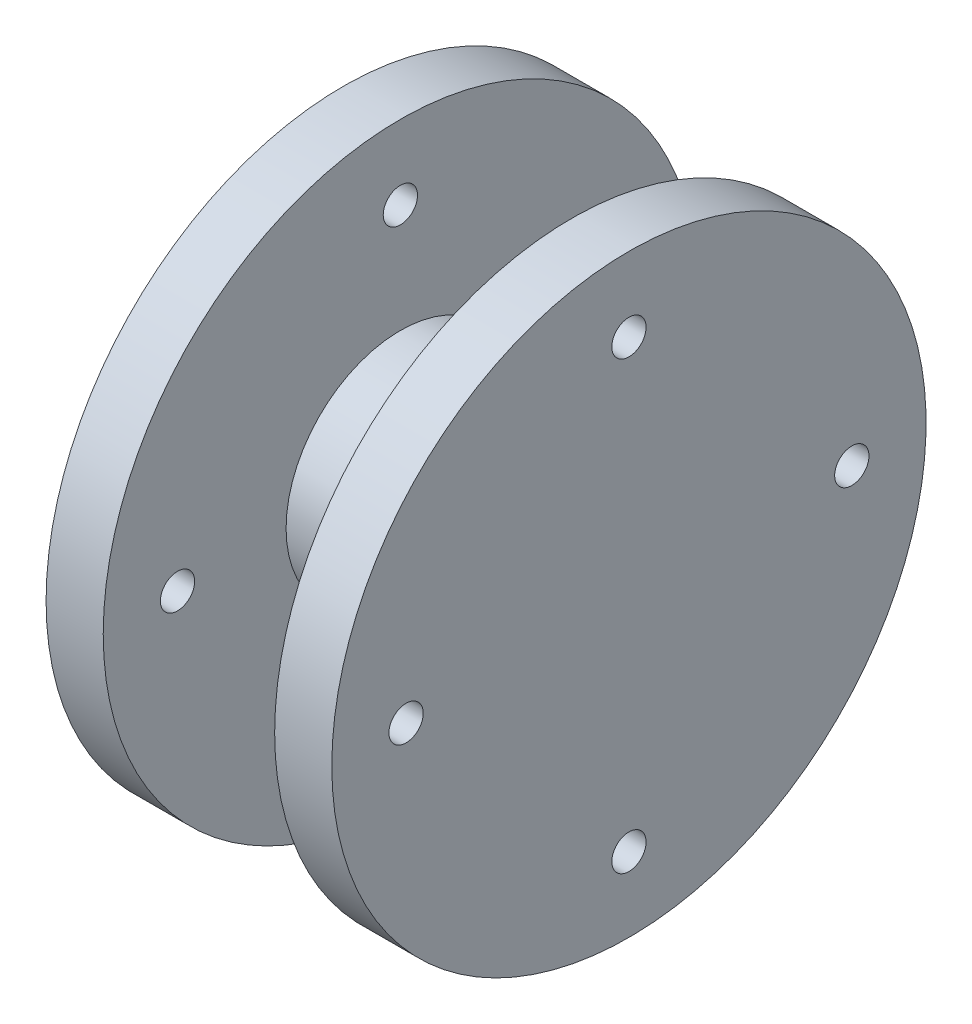
SolidWorks part; units mm, degrees
ref_plane "Спереди" through (0, 0, 0) normal (0, 0, 1) x (1, 0, 0)
ref_plane "Сверху" through (0, 0, 0) normal (0, 1, 0) x (1, 0, 0)
ref_plane "Справа" through (0, 0, 0) normal (1, 0, 0) x (0, 0, -1)
sketch "Эскиз1" plane through (0, 0, 0) normal (0, 0, 1) x (1, 0, 0)
  line L0 (0, 0) -> (79.0641, 0) construction
  line L1 (0, 0) -> (0, 26)
  line L2 (0, 26) -> (5, 26)
  line L3 (5, 26) -> (5, 10)
  line L4 (5, 10) -> (20, 10)
  line L5 (20, 10) -> (20, 26)
  line L6 (20, 26) -> (25, 26)
  line L7 (25, 26) -> (25, 0)
  line L8 (0, 0) -> (25, 0)
  point P10 (79.0641, 0)
  dimension "D1" = 52
  dimension "D2" = 52
  dimension "D3" = 5
  dimension "D4" = 15
  dimension "D5" = 5
  dimension "D6" = 20
revolve "Повернуть1" add sketch "Эскиз1" angle 360 about L0
sketch "Эскиз2" plane through (0, 0, 0) normal (-1, 0, 0) x (0, 0, 1)
  line L0 (50, 0) -> (-50, 0) construction
  circle A0 centre (0, 19.5) radius 1.5
  dimension "D1" = 3
  dimension "D2" = 19.5
  dimension "D3" = 19.5
extrude "Вырез-Вытянуть1" cut sketch "Эскиз2" against normal through all
ref_axis "Ось1" through (5, 0, 0) along (-1, 0, 0)
pattern_circular "Круговой массив1" count 4 over 360 about axis through (5, 0, 0) along (-1, 0, 0) of "Вырез-Вытянуть1"
